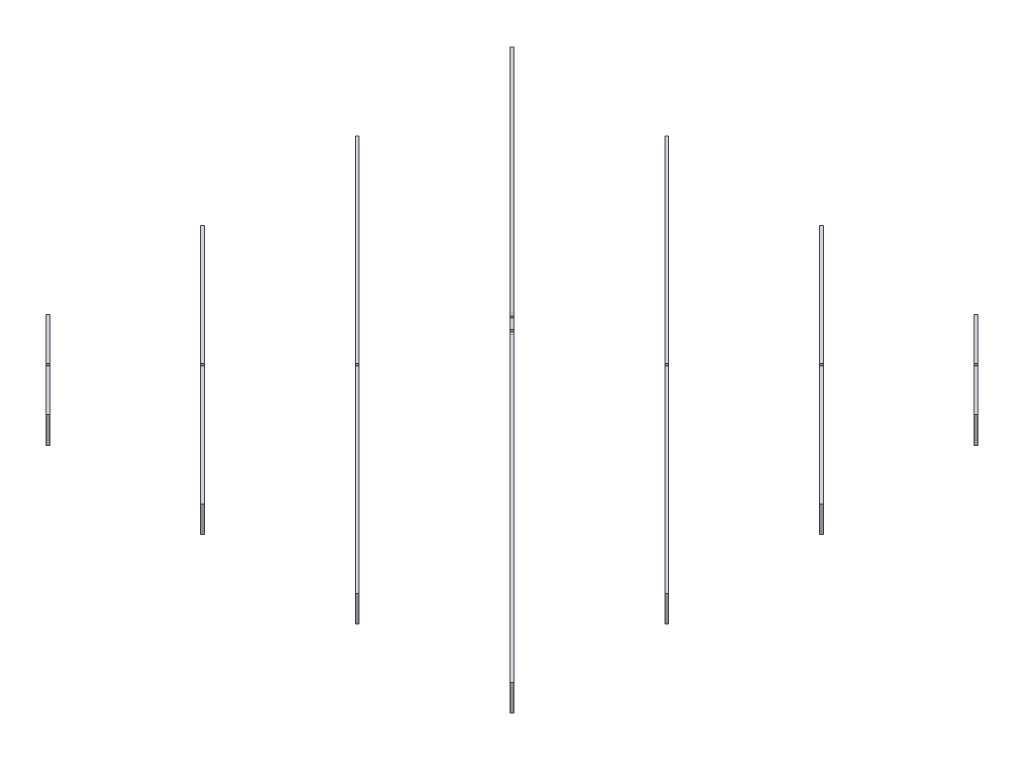
SolidWorks part; units mm, degrees
material "1.0553 (S355J0)"
ref_plane "Front" through (0, 0, 0) normal (0, 0, 1) x (1, 0, 0)
ref_plane "Top" through (0, 0, 0) normal (0, 1, 0) x (1, 0, 0)
ref_plane "Right" through (0, 0, 0) normal (1, 0, 0) x (0, 0, -1)
sketch "Sketch1" plane through (0, 0, 0) normal (0, 1, 0) x (1, 0, 0)
  line L0 (-525, -525) -> (-525, 525) construction
  line L1 (-625, 625) -> (625, 625) construction
  line L2 (-625, 625) -> (-625, -625) construction
  line L3 (-625, -625) -> (625, -625) construction
  line L4 (625, 625) -> (625, -625) construction
  line L5 (-625, 625) -> (625, -625) construction
  line L6 (-625, -625) -> (625, 625) construction
  line L7 (-525, 525) -> (525, 525) construction
  line L8 (-525, 350) -> (525, 350) construction
  line L9 (-525, 175) -> (525, 175) construction
  line L10 (-525, 0) -> (525, 0) construction
  line L11 (-525, -175) -> (525, -175) construction
  line L12 (-525, -350) -> (525, -350) construction
  line L13 (-525, -525) -> (525, -525) construction
  line L14 (-350, -525) -> (-350, 525) construction
  line L15 (-175, -525) -> (-175, 525) construction
  line L16 (0, -525) -> (0, 525) construction
  line L17 (175, -525) -> (175, 525) construction
  line L18 (350, -525) -> (350, 525) construction
  line L19 (525, -525) -> (525, 525) construction
  line L20 (625, 620) -> (625, -620) construction
  line L21 (620, -625) -> (-620, -625) construction
  point P0 (0, 0)
  dimension "D5" = 175
  dimension "D3" = 7
  dimension "D4" = 7
sketch "Sketch2" plane through (0, 0, 0) normal (0, 1, 0) x (1, 0, 0)
  line L0 (-625, 625) -> (625, -625) construction
  line L1 (622.8787, -622.8787) -> (-622.8787, -622.8787) construction
  line L2 (622.8787, -622.8787) -> (622.8787, 622.8787) construction
  line L3 (622.8787, 622.8787) -> (-622.8787, 622.8787) construction
  line L4 (-622.8787, -622.8787) -> (-622.8787, 622.8787) construction
  line L5 (622.8787, -622.8787) -> (-622.8787, 622.8787) construction
  line L6 (622.8787, 622.8787) -> (-622.8787, -622.8787) construction
  line L7 (-272.8787, 622.8787) -> (622.8787, -272.8787) construction
  line L8 (77.1213, 622.8787) -> (622.8787, 77.1213) construction
  line L9 (427.1213, 622.8787) -> (622.8787, 427.1213) construction
  line L10 (-622.8787, 272.8787) -> (272.8787, -622.8787) construction
  line L11 (-622.8787, -77.1213) -> (-77.1213, -622.8787) construction
  line L12 (-622.8787, -427.1213) -> (-427.1213, -622.8787) construction
  line L13 (-625, -429.2426) -> (-429.2426, -625)
  line L14 (-625, -79.2426) -> (-79.2426, -625)
  line L15 (-625, 270.7574) -> (270.7574, -625)
  line L16 (625, -620.7574) -> (-620.7574, 625)
  line L17 (-275, 620.7574) -> (620.7574, -275)
  line L18 (75, 620.7574) -> (620.7574, 75)
  line L19 (425, 620.7574) -> (620.7574, 425)
  line L20 (-620.7574, -425) -> (-425, -620.7574)
  line L21 (-620.7574, -75) -> (-75, -620.7574)
  line L22 (-620.7574, 275) -> (275, -620.7574)
  line L23 (620.7574, -625) -> (-625, 620.7574)
  line L24 (-270.7574, 625) -> (625, -270.7574)
  line L25 (79.2426, 625) -> (625, 79.2426)
  line L26 (429.2426, 625) -> (625, 429.2426)
  line L27 (-625, 625) -> (625, 625) construction
  line L29 (-625, -429.2426) -> (-620.7574, -425)
  line L30 (-429.2426, -625) -> (-425, -620.7574)
  line L31 (-625, -79.2426) -> (-620.7574, -75)
  line L32 (-79.2426, -625) -> (-75, -620.7574)
  line L33 (-625, 270.7574) -> (-620.7574, 275)
  line L34 (270.7574, -625) -> (275, -620.7574)
  line L35 (625, -620.7574) -> (620.7574, -625)
  line L36 (-620.7574, 625) -> (-625, 620.7574)
  line L37 (-275, 620.7574) -> (-270.7574, 625)
  line L38 (620.7574, -275) -> (625, -270.7574)
  line L39 (75, 620.7574) -> (79.2426, 625)
  line L40 (620.7574, 75) -> (625, 79.2426)
  line L41 (425, 620.7574) -> (429.2426, 625)
  line L42 (620.7574, 425) -> (625, 429.2426)
  point P0 (0, 0)
extrude "Boss-Extrude1" add sketch "Sketch2" along normal blind 60
sketch "Sketch4" plane through (-2.1213, 0, 2.1213) normal (-0.7071, 0, 0.7071) x (0.7071, 0, 0.7071)
  line L0 (0, 60) -> (0, 140) construction
  line L1 (-138.4214, 60) -> (138.4214, 60) construction
  line L2 (-30, 140) -> (-880.8835, 60)
  line L3 (-880.8835, 60) -> (-30, 60)
  line L4 (-30, 60) -> (-30, 140) construction
  line L5 (30, 140) -> (-30, 140)
  line L6 (880.8835, 60) -> (30, 60)
  line L7 (30, 140) -> (880.8835, 60)
  line L8 (-30, 60) -> (30, 60)
  dimension "D1" = 80
  dimension "D2" = 30
extrude "Boss-Extrude2" add sketch "Sketch4" against normal up to vertex (6 mm away) up to point (625, 60, 620.7574)
sketch "Sketch5" plane through (-527.1213, 0, 527.1213) normal (-0.7071, 0, 0.7071) x (0.7071, 0, 0.7071)
  line L0 (-742.4621, 0) -> (0, 0) construction
  line L1 (-745.4621, 30) -> (-739.4621, 30)
  line L2 (-745.4621, 30) -> (-745.4621, -30)
  line L3 (-745.4621, -30) -> (-739.4621, -30)
  line L4 (-739.4621, 30) -> (-739.4621, -30)
  line L5 (-745.4621, 30) -> (-739.4621, -30) construction
  line L6 (-745.4621, -30) -> (-739.4621, 30) construction
  line L7 (-883.8835, 0) -> (883.8835, 0) construction
  line L8 (247.4874, 0) -> (-494.9747, 0) construction
  line L9 (-497.9747, 30) -> (-491.9747, 30)
  line L10 (-497.9747, 30) -> (-497.9747, -30)
  line L11 (-497.9747, -30) -> (-491.9747, -30)
  line L12 (-491.9747, 30) -> (-491.9747, -30)
  line L13 (-497.9747, 30) -> (-491.9747, -30) construction
  line L14 (-497.9747, -30) -> (-491.9747, 30) construction
  line L15 (123.7437, 0) -> (-618.7184, 0) construction
  line L16 (-250.4874, 30) -> (-244.4874, 30)
  line L17 (-250.4874, 30) -> (-250.4874, -30)
  line L18 (-250.4874, -30) -> (-244.4874, -30)
  line L19 (-244.4874, 30) -> (-244.4874, -30)
  line L20 (-250.4874, 30) -> (-244.4874, -30) construction
  line L21 (-250.4874, -30) -> (-244.4874, 30) construction
  line L22 (0, 0) -> (0, 140) construction
  line L27 (30, 140) -> (-30, 140) construction
  line L28 (250.4874, -30) -> (244.4874, 30) construction
  line L29 (250.4874, 30) -> (244.4874, -30) construction
  line L30 (497.9747, -30) -> (491.9747, 30) construction
  line L31 (497.9747, 30) -> (491.9747, -30) construction
  line L32 (745.4621, -30) -> (739.4621, 30) construction
  line L33 (745.4621, 30) -> (739.4621, -30) construction
  line L34 (244.4874, 30) -> (244.4874, -30)
  line L35 (250.4874, -30) -> (244.4874, -30)
  line L36 (250.4874, 30) -> (250.4874, -30)
  line L37 (250.4874, 30) -> (244.4874, 30)
  line L38 (491.9747, 30) -> (491.9747, -30)
  line L39 (497.9747, -30) -> (491.9747, -30)
  line L40 (497.9747, 30) -> (497.9747, -30)
  line L41 (497.9747, 30) -> (491.9747, 30)
  line L42 (739.4621, 30) -> (739.4621, -30)
  line L43 (745.4621, -30) -> (739.4621, -30)
  line L44 (745.4621, 30) -> (745.4621, -30)
  line L45 (745.4621, 30) -> (739.4621, 30)
  circle A0 centre (-745.4621, 30) radius 1.5
  circle A1 centre (-739.4621, 30) radius 1.5
  circle A2 centre (-497.9747, 30) radius 1.5
  circle A3 centre (-491.9747, 30) radius 1.5
  circle A4 centre (-250.4874, 30) radius 1.5
  circle A5 centre (-244.4874, 30) radius 1.5
  circle A6 centre (244.4874, 30) radius 1.5
  circle A7 centre (250.4874, 30) radius 1.5
  circle A8 centre (491.9747, 30) radius 1.5
  circle A9 centre (497.9747, 30) radius 1.5
  circle A10 centre (739.4621, 30) radius 1.5
  circle A11 centre (745.4621, 30) radius 1.5
  point P0 (-742.4621, 0)
  point P9 (-494.9747, 0)
  point P16 (-247.4874, 0)
  point P52 (247.4874, 0)
  point P53 (494.9747, 0)
  point P54 (742.4621, 0)
  dimension "D7" = 3
  dimension "D8" = 3
  dimension "D9" = 3
  dimension "D10" = 3
  dimension "D11" = 3
  dimension "D12" = 3
  dimension "D1" = 3
  dimension "D2" = 3
  dimension "D3" = 3
  dimension "D4" = 60
  dimension "D5" = 60
  dimension "D6" = 60
extrude "Cut-Extrude2" cut sketch "Sketch5" against normal through all contours L1 A0 L2 | L4 A1 L1 | L1 A1 L4 | L2 A0 L1 | A1 L1 A0 L2 L3 L4 | L12 A3 L9 | L9 A3 L12 | A3 L9 A2 L10 L11 L12 | L10 A2 L9 | L9 A2 L10 | L16 A4 L17 | L19 A5 L16 | L16 A5 L19 | L17 A4 L16 | A5 L16 A4 L17 L18 L19 | A6 L34 L37 | A6 L37 L34 | L36 A7 L37 A6 L34 L35 | A7 L36 L37 | A7 L37 L36 | A8 L38 L41 | A8 L41 L38 | L40 A9 L41 A8 L38 L39 | A9 L40 L41 | A9 L41 L40 | A10 L42 L45 | A10 L45 L42 | L44 A11 L45 A10 L42 L43 | A11 L44 L45 | A11 L45 L44 region at (-1054.3927, 30.2122, -0.1501) region at (-1053.7925, 29.3634, 0.4502) region at (-1052.1213, -0.2911, 2.1213) region at (-1049.8499, 30.2122, 4.3927) region at (-1050.4502, 29.3634, 3.7925) region at (-879.3927, 30.2122, 174.8499) region at (-878.7925, 29.3634, 175.4502) region at (-877.1213, -0.2911, 177.1213) region at (-874.8499, 30.2122, 179.3927) region at (-875.4502, 29.3634, 178.7925) region at (-704.3927, 30.2122, 349.8499) region at (-703.7925, 29.3634, 350.4502) region at (-702.1213, -0.2911, 352.1213) region at (-699.8499, 30.2122, 354.3927) region at (-700.4502, 29.3634, 353.7925) region at (-353.7925, 29.3634, 700.4502) region at (-354.3927, 30.2122, 699.8499) region at (-352.1213, -0.2911, 702.1213) region at (-349.8499, 30.2122, 704.3927) region at (-350.4502, 29.3634, 703.7925) region at (-178.7925, 29.3634, 875.4502) region at (-179.3927, 30.2122, 874.8499) region at (-177.1213, -0.2911, 877.1213) region at (-174.8499, 30.2122, 879.3927) region at (-175.4502, 29.3634, 878.7925) region at (-3.7925, 29.3634, 1050.4502) region at (-4.3927, 30.2122, 1049.8499) region at (-2.1213, -0.2911, 1052.1213) region at (0.1501, 30.2122, 1054.3927) region at (-0.4502, 29.3634, 1053.7925)
sketch "Sketch6" plane through (-527.1213, 0, 527.1213) normal (-0.7071, 0, 0.7071) x (0.7071, 0, 0.7071)
  line L0 (-138.4214, 60) -> (138.4214, 60) construction
  line L1 (-3, 90) -> (3, 90)
  line L2 (-3, 90) -> (-3, 30)
  line L3 (-3, 30) -> (3, 30)
  line L4 (3, 90) -> (3, 30)
  line L5 (-3, 90) -> (3, 30) construction
  line L6 (-3, 30) -> (3, 90) construction
  line L7 (0, 60) -> (0, 0) construction
  circle A0 centre (-3, 30) radius 1.5
  circle A1 centre (3, 30) radius 1.5
  point P0 (0, 60)
  point P10 (0, 30)
  line M8 (138.4214, 60) -> (-138.4214, 60)
  dimension "D1" = 3
  dimension "D2" = 3
  dimension "D3" = 3
extrude "Cut-Extrude3" cut sketch "Sketch6" along normal up to surface (-989.9495 mm away) from surface contours A1 L4 L2 A0 L3 M8 | L3 A1 L4 | L2 A0 L3 | L3 A0 L2 | L4 A1 L3 region at (-527.1213, 45.2877, 527.1213) region at (-528.7925, 30.6366, 525.4502) region at (-529.3927, 29.7878, 524.8499) region at (-524.8499, 29.7878, 529.3927) region at (-525.4502, 30.6366, 528.7925) up to face at (172.8787, 21.5173, -172.8787) starting at face at (527.1213, 30, -527.1213)
sketch "Sketch8" plane through (-527.1213, 0, 527.1213) normal (-0.7071, 0, 0.7071) x (0.7071, 0, 0.7071)
  line L4 (3, 90) -> (-3, 90)
  line L5 (3, 30) -> (3, 90)
  line L6 (-3, 30) -> (3, 30)
  line L7 (-3, 90) -> (-3, 30)
  line L8 (3, 90) -> (-3, 90)
  line L9 (3, 30) -> (3, 90)
  line L10 (-3, 30) -> (3, 30)
  line L11 (-3, 90) -> (-3, 30)
  circle A1 centre (3, 30) radius 1.5
  circle A2 centre (3, 30) radius 1.5
  circle A3 centre (-3, 30) radius 1.5
  circle A4 centre (-3, 30) radius 1.5
  line M9 (138.4214, 60) -> (-138.4214, 60)
  dimension "D1" = 0
  dimension "D2" = 0
  dimension "D3" = 0
extrude "Cut-Extrude4" cut sketch "Sketch8" against normal up to surface (500.9747 mm away) contours A4 L10 A2 L9 L11 M9 | L10 A2 L9 | L11 A4 L10 | L10 A4 L11 | L9 A2 L10 region at (-527.1213, 45.2877, 527.1213) region at (-524.8499, 29.7878, 529.3927) region at (-525.4502, 30.6366, 528.7925) region at (-528.7925, 30.6366, 525.4502) region at (-529.3927, 29.7878, 524.8499) up to face at (-172.8787, 21.5173, 172.8787)
sketch "Sketch9" plane through (-2.1213, 0, 2.1213) normal (-0.7071, 0, 0.7071) x (0.7071, 0, 0.7071)
  line L0 (0, 0) -> (0, 140) construction
  line L1 (30, 140) -> (-30, 140) construction
  line L3 (-3, -70) -> (3, -70)
  line L4 (-3, -70) -> (-3, 70)
  line L5 (-3, 70) -> (3, 70)
  line L6 (3, -70) -> (3, 70)
  line L7 (-3, -70) -> (3, 70) construction
  line L8 (-3, 70) -> (3, -70) construction
  circle A0 centre (-3, 70) radius 1.5
  circle A1 centre (3, 70) radius 1.5
  point P9 (0, 70)
  line M18 (-244.4874, 0) -> (244.4874, 0)
  dimension "D1" = 3
  dimension "D2" = 3
  dimension "D3" = 3
extrude "Cut-Extrude5" cut sketch "Sketch9" against normal up to next (6 mm away) contours A1 L5 A0 L4 L6 M18 | L6 A1 L5 | L5 A0 L4 | L4 A0 L5 | L5 A1 L6 region at (-2.1213, 34.7084, 2.1213) region at (-4.3927, 70.2122, -0.1501) region at (-3.7925, 69.3634, 0.4502) region at (-0.4502, 69.3634, 3.7925) region at (0.1501, 70.2122, 4.3927)
sketch "Sketch10" plane through (-2.1213, 0, 2.1213) normal (-0.7071, 0, 0.7071) x (0.7071, 0, 0.7071)
  line L0 (0, 70) -> (0, 140) construction
  line L1 (-1.5, 70) -> (1.5, 70) construction
  line L2 (30, 140) -> (-30, 140) construction
  line L3 (-16, 140) -> (-22, 120) construction
  line L4 (16, 120) -> (22, 120)
  line L5 (16, 120) -> (16, 140)
  line L6 (16, 140) -> (22, 140)
  line L7 (22, 120) -> (22, 140)
  line L8 (16, 120) -> (22, 140) construction
  line L9 (16, 140) -> (22, 120) construction
  line L10 (-16, 120) -> (-22, 140) construction
  line L11 (-22, 120) -> (-22, 140)
  line L12 (-16, 140) -> (-22, 140)
  line L13 (-16, 120) -> (-16, 140)
  line L14 (-16, 120) -> (-22, 120)
  circle A0 centre (16, 120) radius 1.5
  circle A1 centre (22, 120) radius 1.5
  circle A2 centre (-22, 120) radius 1.5
  circle A3 centre (-16, 120) radius 1.5
  point P6 (19, 130)
  point P20 (-19, 130)
  line M29 (30, 140) -> (-30, 140)
  dimension "D1" = 3
  dimension "D3" = 3
  dimension "D4" = 3
  dimension "D2" = 20
  dimension "D5" = 32
extrude "Cut-Extrude6" cut sketch "Sketch10" against normal through all contours L4 A1 L7 | L7 A1 L4 | A1 L7 L5 A0 L4 M29 | L4 A0 L5 | L5 A0 L4 | A3 L13 L14 | A3 L14 L13 | L14 A3 L13 L11 A2 M29 | A2 L11 L14 | A2 L14 L11 region at (9.6425, 120.6366, 13.8852) region at (9.0423, 119.7878, 13.285) region at (11.3137, 130.2841, 15.5563) region at (-15.5563, 130.2841, -11.3137) region at (12.9849, 120.6366, 17.2275) region at (13.5851, 119.7878, 17.8277) region at (-13.285, 119.7878, -9.0423) region at (-13.8852, 120.6366, -9.6425) region at (-17.2275, 120.6366, -12.9849) region at (-17.8277, 119.7878, -13.5851)
equation "\"D1@Boss-Extrude1\"=\"Plate width\""
equation "\"Plate width\"= 60"
equation "\"D1@Sketch5\"=\"Half rib thickness\""
equation "\"D2@Sketch5\"=\"Half rib thickness\""
equation "\"D3@Sketch5\"=\"Half rib thickness\""
equation "\"D4@Sketch5\"=\"Plate width\""
equation "\"D5@Sketch5\"=\"Plate width\""
equation "\"D6@Sketch5\"=\"Plate width\""
equation "\"D7@Sketch5\"=\"Half rib thickness\""
equation "\"D8@Sketch5\"=\"Half rib thickness\""
equation "\"D9@Sketch5\"=\"Half rib thickness\""
equation "\"D10@Sketch5\"=\"Half rib thickness\""
equation "\"D11@Sketch5\"=\"Half rib thickness\""
equation "\"D12@Sketch5\"=\"Half rib thickness\""
equation "\"D1@Sketch6\"=\"Half rib thickness\""
equation "\"D2@Sketch6\"=\"Half rib thickness\""
equation "\"D3@Sketch6\"=\"Half rib thickness\""
equation "\"D1@Sketch9\"=\"Half rib thickness\""
equation "\"D2@Sketch9\"=\"Half rib thickness\""
equation "\"D3@Sketch9\"=\"Half rib thickness\""
equation "\"D1@Sketch10\"=\"Half rib thickness\""
equation "\"D3@Sketch10\"=\"Half rib thickness\""
equation "\"D4@Sketch10\"=\"Half rib thickness\""
